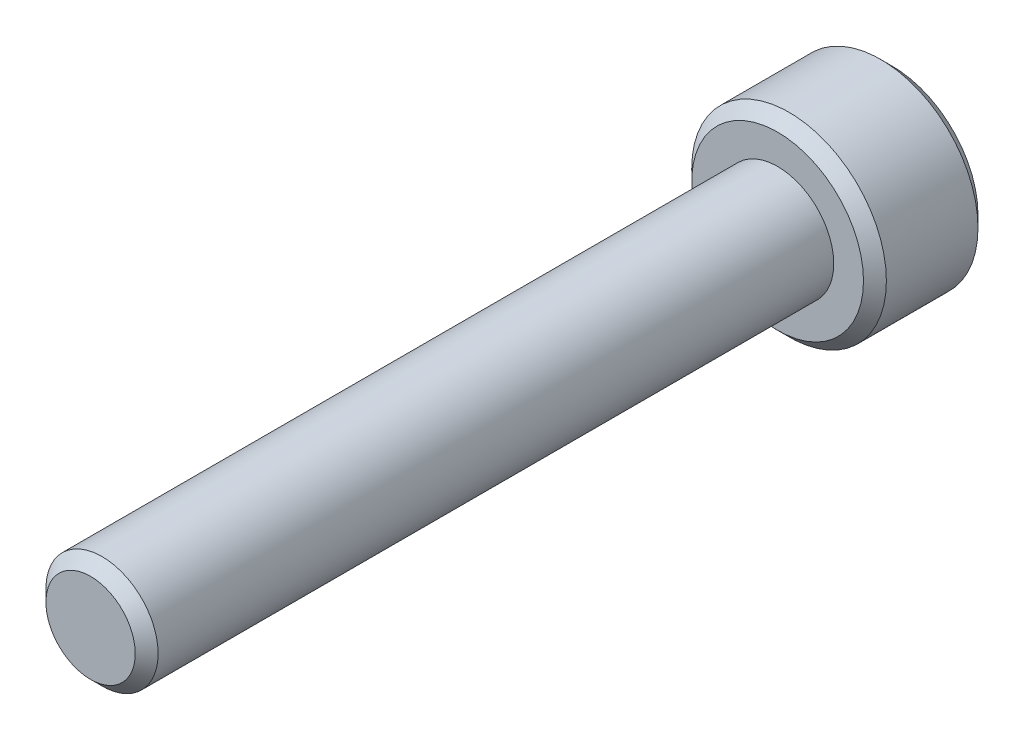
SolidWorks part; units mm, degrees
ref_plane "Front" through (0, 0, 0) normal (0, 0, 1) x (1, 0, 0)
ref_plane "Top" through (0, 0, 0) normal (0, 1, 0) x (1, 0, 0)
ref_plane "Right" through (0, 0, 0) normal (1, 0, 0) x (0, 0, -1)
sketch "Skizze1" plane through (0, 0, 0) normal (0, 0, 1) x (1, 0, 0)
  circle A0 centre (0, 0) radius 2.45
  circle A1 centre (0, 0) radius 4.25
  dimension "D1" = 8.5
  dimension "D2" = 4.9
extrude "Aufsatz-Linear austragen1" add sketch "Skizze1" along normal blind 5 contours A0 | A1 A0 region at (0, 0, 0) region at (-4.1298, 0, 0)
extrude "Aufsatz-Linear austragen2" add sketch "Skizze1<3>" along normal blind 35 contours A0 region at (0, 0, 0)
sketch "Skizze1<3>" plane through (0, 0, 0) normal (0, 0, 1) x (1, 0, 0) same geometry as "Skizze1"
chamfer "Fase1" distance 0.5 angle 45 3 edges at (4.25, 0, 0) (4.25, 0, 5) (2.45, 0, 35)
